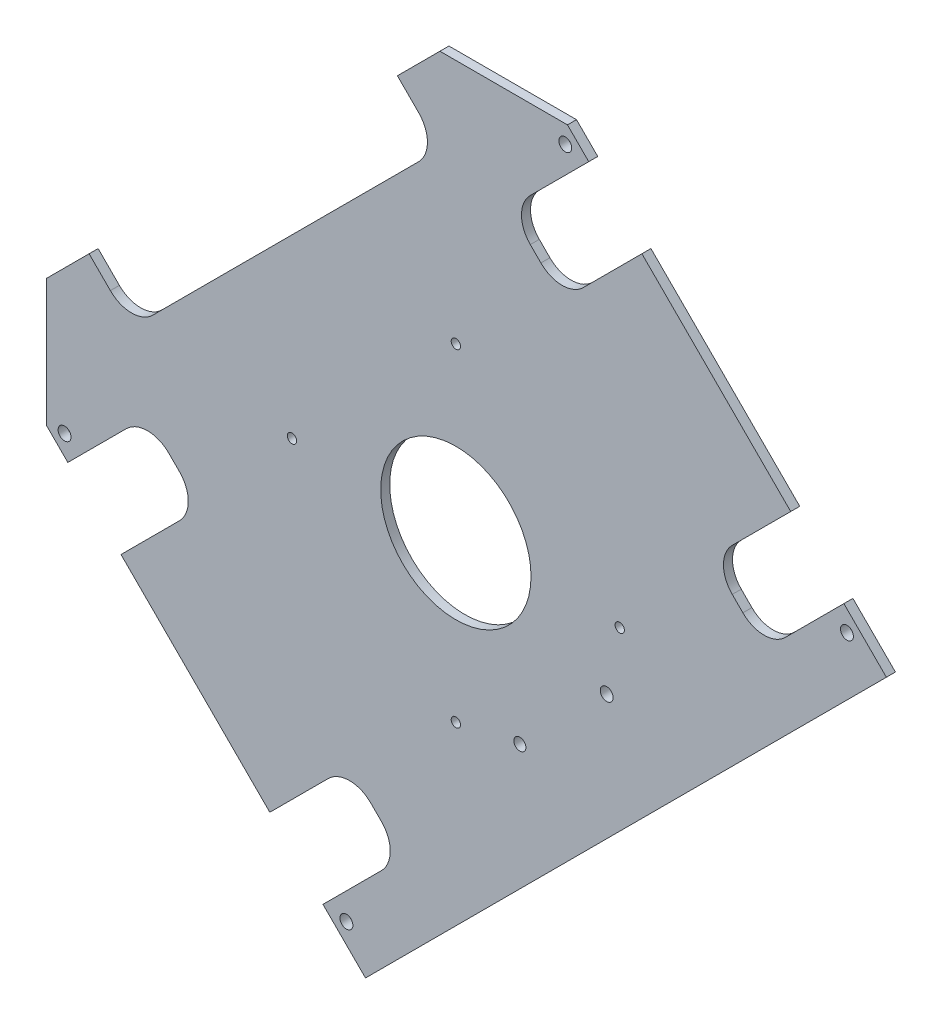
SolidWorks part; units mm, degrees
ref_plane "前视基准面" through (0, 0, 0) normal (0, 0, 1) x (1, 0, 0)
ref_plane "上视基准面" through (0, 0, 0) normal (0, 1, 0) x (1, 0, 0)
ref_plane "右视基准面" through (0, 0, 0) normal (1, 0, 0) x (0, 0, -1)
sketch "Sketch1" plane through (0, 0, 0) normal (0, 0, 1) x (1, 0, 0)
  line L16 (44.1941, 129.0469) -> (15.9098, 157.3312)
  line L17 (-110.8692, -62.3719) -> (-111.3693, -61.8718)
  line L18 (15.9098, 157.3312) -> (-19.4455, 121.9759)
  line L20 (61.1787, 112.0623) -> (111.3693, 61.8718)
  line L21 (-110.8692, -62.3719) -> (-61.8718, -111.3693)
  line L22 (143.1891, 30.052) -> (-30.052, -143.1891)
  line L23 (10.9602, -120.5617) -> (86.6206, -196.2221) construction
  line L24 (196.2221, -86.6206) -> (120.5617, -10.9602) construction
  line L25 (120.5617, -6.7176) -> (141.7749, 14.4956) construction
  line L26 (14.4956, 141.7749) -> (-6.7176, 120.5617) construction
  line L27 (61.1787, 112.0623) -> (61.8718, 111.3693)
  line L28 (44.1941, 129.0469) -> (17.6776, 102.5304)
  line L29 (61.8718, 111.3693) -> (35.3553, 84.8528)
  line L30 (17.6776, 102.5304) -> (35.3553, 84.8528)
  line L32 (111.3693, 61.8718) -> (84.8528, 35.3553)
  line L33 (129.0469, 44.1941) -> (102.5304, 17.6776)
  line L34 (84.8528, 35.3553) -> (102.5304, 17.6776)
  line L35 (56.5685, -56.5685) -> (-56.5685, 56.5685) construction
  line L36 (-35.3553, -84.8528) -> (-17.6776, -102.5304)
  line L37 (-44.1941, -129.0469) -> (-17.6776, -102.5304)
  line L38 (-61.8718, -111.3693) -> (-35.3553, -84.8528)
  line L40 (-102.5304, -17.6776) -> (-84.8528, -35.3553)
  line L41 (-111.3693, -61.8718) -> (-84.8528, -35.3553)
  line L42 (-129.0469, -44.1941) -> (-102.5304, -17.6776)
  line L44 (48.0832, 104.6517) -> (37.4766, 94.0451) construction
  line L45 (94.0451, 37.4766) -> (104.6517, 48.0832) construction
  line L46 (115.2584, 37.4766) -> (104.6517, 26.87) construction
  line L47 (102.5304, 24.7487) -> (98.9949, 28.2842) construction
  line L48 (28.2842, 98.9949) -> (24.7487, 102.5304) construction
  line L50 (-121.9759, 19.4455) -> (-107.8337, 5.3034)
  line L51 (-19.4455, 121.9759) -> (-5.3034, 107.8337)
  line L52 (-107.8337, 5.3034) -> (-5.3034, 107.8337)
  line L53 (-121.9759, 19.4455) -> (-157.3312, -15.9098)
  line L54 (129.0469, 44.1941) -> (143.1891, 30.052)
  line L55 (-129.0469, -44.1941) -> (-157.3312, -15.9098)
  line L56 (-44.1941, -129.0469) -> (-30.052, -143.1891)
  circle A0 centre (0, -54.5) radius 1.55 construction
  circle A1 centre (54.5, 0) radius 1.55 construction
  circle A2 centre (-54.5, 0) radius 1.55 construction
  circle A3 centre (0, 54.5) radius 1.55 construction
  circle A4 centre (0, -54.5) radius 1.55
  circle A5 centre (54.5, 0) radius 1.55
  circle A6 centre (-54.5, 0) radius 1.55
  circle A7 centre (0, 54.5) radius 1.55
  circle A8 centre (0, 0) radius 25
  circle A9 centre (50.1675, -21.2948) radius 2.15 construction
  circle A10 centre (21.2948, -50.1675) radius 2 construction
  circle A11 centre (21.2948, -50.1675) radius 2
  circle A12 centre (50.1675, -21.2948) radius 2.15
  point P53 (99.3484, 42.7799)
  dimension "D1" = 45
  dimension "D2" = 45
  dimension "D3" = 10
  dimension "D4" = 10
  dimension "D5" = 5
  dimension "D6" = 5
  dimension "D7" = 5
  dimension "D8" = 5
  dimension "D9" = 5
  dimension "D10" = 5
  dimension "D11" = 20
  dimension "D12" = 50
  dimension "D13" = 50
extrude "Extrude1" add sketch "Sketch1" along normal blind 3 contours L22 L35 A8 L52 L50 L53 L55 L42 L40 L41 L17 L21 L38 L36 L37 L56 A4 A6 A11 | L35 L22 L54 L33 L34 L32 L20 L29 L30 L28 L16 L18 L51 L52 A8 A12 A7 A5 region at (39.9762, 47.2202, 0) region at (-47.2126, -39.9774, 0)
fillet "Fillet1" radius 10 2 edges at (-5.3034, 107.8337, 1.5) (-107.8337, 5.3034, 1.5)
fillet "Fillet2" radius 10 8 edges at (35.3553, 84.8528, 1.5) (17.6776, 102.5304, 1.5) (84.8528, 35.3553, 1.5) (102.5304, 17.6776, 1.5) (-17.6776, -102.5304, 1.5) (-35.3553, -84.8528, 1.5) (-84.8528, -35.3553, 1.5) (-102.5304, -17.6776, 1.5)
chamfer "Chamfer1" distance 30 angle 45 2 edges at (-157.3312, -15.9098, 1.5) (15.9098, 157.3312, 1.5)
sketch "Sketch3" plane through (0, 0, 3) normal (0, 0, 1) x (1, 0, 0)
  circle A0 centre (130.064, 36.3235) radius 2.15 construction
  circle A1 centre (36.3942, 130.1348) radius 2.15 construction
  circle A2 centre (-36.3942, -130.1348) radius 2.15 construction
  circle A3 centre (-130.1348, -36.3942) radius 2.15 construction
  circle A4 centre (130.064, 36.3235) radius 2.15
  circle A5 centre (36.3942, 130.1348) radius 2.15
  circle A6 centre (-36.3942, -130.1348) radius 2.15
  circle A7 centre (-130.1348, -36.3942) radius 2.15
extrude "Cut-Extrude1" cut sketch "Sketch3" against normal blind 3
